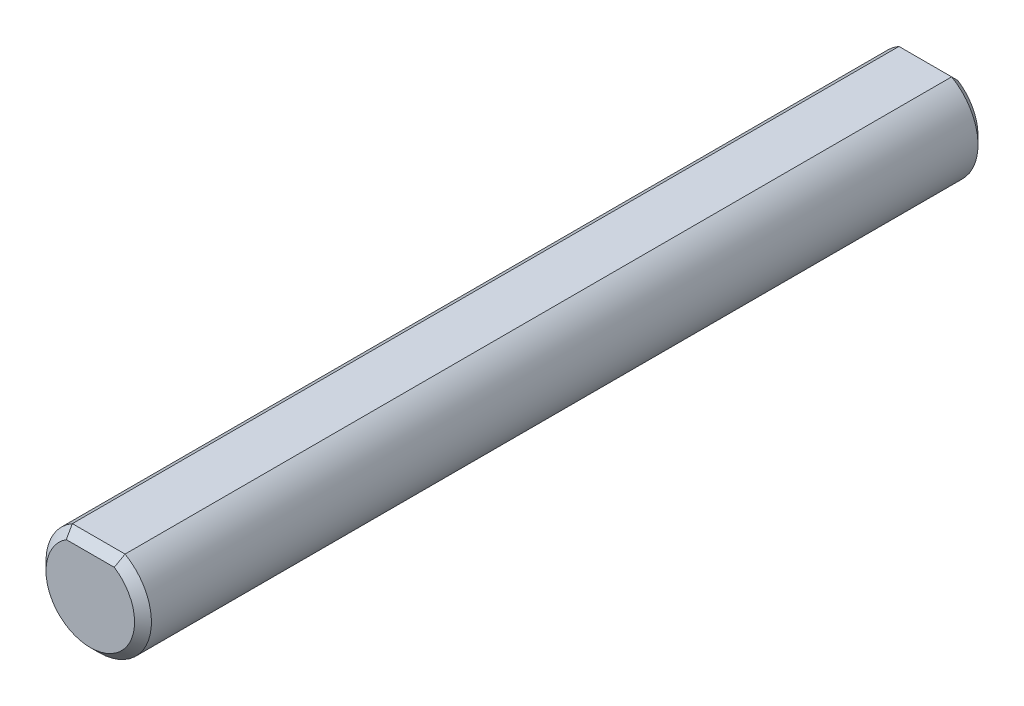
SolidWorks part; units mm, degrees
ref_plane "Front Plane" through (0, 0, 0) normal (0, 0, 1) x (1, 0, 0)
ref_plane "Top Plane" through (0, 0, 0) normal (0, 1, 0) x (1, 0, 0)
ref_plane "Right Plane" through (0, 0, 0) normal (1, 0, 0) x (0, 0, -1)
sketch "Sketch1" plane through (0, 0, 0) normal (0, 0, 1) x (1, 0, 0)
  line L0 (-1.5875, 2.7496) -> (1.5875, 2.7496)
  arc A0 (-1.5875, 2.7496) -> (1.5875, 2.7496) centre (0, 0) ccw
  dimension "D1" = 6.35
  dimension "D2" = 3.175
extrude "Boss-Extrude1" add sketch "Sketch1" along normal blind 50.8
chamfer "Chamfer1" distance 0.508 angle 45 4 edges at (0, 2.7496, 50.8) (0, -3.175, 50.8) (0, 2.7496, 0) (0, -3.175, 0)
